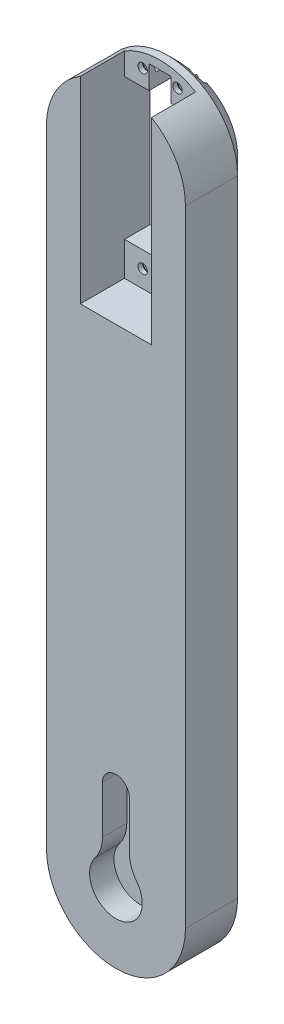
SolidWorks part; units mm, degrees
ref_plane "Front Plane" through (0, 0, 0) normal (0, 0, 1) x (1, 0, 0)
ref_plane "Top Plane" through (0, 0, 0) normal (0, 1, 0) x (1, 0, 0)
ref_plane "Right Plane" through (0, 0, 0) normal (1, 0, 0) x (0, 0, -1)
sketch "Sketch1" plane through (0, 0, 0) normal (0, 0, 1) x (1, 0, 0)
  line L0 (0, 0) -> (0, 147.804) construction
  line L4 (0, 180) -> (0, 0) construction
  line L6 (20, 180) -> (20, 0)
  line L7 (-20, 180) -> (-20, 0)
  arc A1 (20, 180) -> (-20, 180) centre (0, 180) ccw
  arc A2 (-20, 0) -> (20, 0) centre (0, 0) ccw
  point P2 (0, 0)
  point P7 (0, 90)
  dimension "D1" = 180
  dimension "D3" = 40
extrude "Boss-Extrude1" add sketch "Sketch1" along normal mid plane 20
chamfer "Chamfer1" distance 5 angle 45 4 edges at (-20, 90, -10) (0, -20, -10) (20, 90, -10) (0, 200, -10)
sketch "Sketch3" plane through (0, 0, 0) normal (1, 0, 0) x (0, 0, -1)
  line L0 (-10, 170.5) -> (30.3, 170.5) construction
  line L2 (2.7, 190.79) -> (2.7, 200.5)
  line L3 (2.7, 200.5) -> (-10, 200.5)
  line L5 (2.7, 190.79) -> (10, 190.79)
  line L7 (10, 190.79) -> (10, 170.5)
  line L8 (-10, 0) -> (-10, 180) construction
  line L9 (10, 170.5) -> (-10, 170.5)
  line L10 (10, 0) -> (10, 180) construction
  line L11 (-10, 170.5) -> (-10, 200.5)
  line L12 (30.3, 151.5) -> (30.3, 189.5) construction
  line L13 (30.3, 151.5) -> (30.3, 189.5) construction
  dimension "D1" = 20.29
  dimension "D2" = 30
  dimension "D3" = 12.7
extrude "Cut-Extrude1" cut sketch "Sketch3" against normal mid plane 20.5
sketch "Sketch11" plane through (0, 0, -2.7) normal (0, 0, 1) x (1, 0, 0)
  line L0 (-8.25, 195.5) -> (8.25, 195.5) construction
  arc A0 (-7.6279, 197.0532) -> (-4.4736, 197.1531) centre (-6, 195.5) ccw construction
  arc A1 (4.4736, 197.1531) -> (7.6279, 197.0532) centre (6, 195.5) ccw construction
  circle A2 centre (-5, 195.5) radius 2
  dimension "D1" = 4
  dimension "D2" = 1
ref_axis "Axis1" through (-6, 195.5, 15.691) along (0, 0, 1)
ref_plane "Plane1" through (-5, 0, 0) normal (1, 0, 0) x (0, 0, -1)
sketch "Sketch4" plane through (-5, 0, 0) normal (1, 0, 0) x (0, 0, -1)
  line L0 (-15.691, 195.5) -> (-20.7621, 195.5) construction
  line L1 (2.7, 195.5) -> (10, 195.5)
  line L2 (2.7, 190.79) -> (2.7, 197.1737) construction
  line L3 (2.7, 195.5) -> (2.7, 196.85)
  line L4 (2.7, 196.85) -> (4, 196.85)
  line L5 (4, 196.85) -> (4.75, 197.6)
  line L6 (4.75, 197.6) -> (10, 197.6)
  line L7 (10, 197.6) -> (10, 195.5)
  line L8 (10, 180) -> (10, 195) construction
  dimension "D1" = 6
  dimension "D2" = 1.35
  dimension "D3" = 2.1
  dimension "D4" = 135
revolve "Cut-Revolve1" cut sketch "Sketch4" angle 360 about L1 reverse direction yes
ref_plane "Plane2" through (0, 0, 0) normal (1, 0, 0) x (0, 0, -1)
mirror "Mirror1" about plane through (0, 0, 0) normal (1, 0, 0) of "Cut-Revolve1"
mirror "Mirror2" about plane through (-10.25, 170.5, -10) normal (0, -1, 0) of "Cut-Extrude1", "Mirror1"
sketch "Sketch5" plane through (0, 0, -2.7) normal (0, 0, 1) x (1, 0, 0)
  line L0 (-10.25, 190.79) -> (10.25, 190.79) construction
  line L1 (-3.2, 190.79) -> (3.2, 190.79)
  line L2 (-3.2, 190.79) -> (-3.2, 197.5)
  line L3 (-3.2, 197.5) -> (3.2, 197.5)
  line L4 (3.2, 190.79) -> (3.2, 197.5)
  line L7 (3.2, 147.5) -> (3.2, 142.5) construction
  line L8 (-3.2, 147.5) -> (-3.2, 142.5) construction
  dimension "D1" = 6.71
extrude "Cut-Extrude2" cut sketch "Sketch5" against normal blind 24
sketch "Sketch6" plane through (0, 0, 10) normal (0, 0, 1) x (1, 0, 0)
  line L0 (0, 0) -> (0, 24.5) construction
  line L1 (3.875, 24.5) -> (3.875, 10.7873)
  line L2 (-3.875, 24.5) -> (-3.875, 10.7873)
  arc A0 (-5.9803, 4.6494) -> (5.9803, 4.6494) centre (0, 0) ccw
  arc A1 (3.875, 24.5) -> (-3.875, 24.5) centre (0, 24.5) ccw
  arc A2 (-3.875, 10.7873) -> (-5.9803, 4.6494) centre (-13.875, 10.7873) cw
  arc A3 (3.875, 10.7873) -> (5.9803, 4.6494) centre (13.875, 10.7873) ccw
  dimension "D1" = 15.15
  dimension "D3" = 7.75
  dimension "D4" = 10
  dimension "D2" = 24.5
extrude "Cut-Extrude3" cut sketch "Sketch6" against normal blind 7 contours A3 L1 A1 L2 A2 A0 region at (0, 8.1019, 10)
sketch "Sketch10" plane through (0, 0, -10) normal (0, 0, -1) x (-1, 0, 0)
  line L0 (0, 0) -> (0, 93.1642) construction
  line L1 (10.25, 140.5) -> (-10.25, 140.5) construction
  line L2 (-5, -21) -> (5, -21)
  line L3 (-5, -21) -> (-5, 137.5)
  line L4 (-5, 137.5) -> (5, 137.5)
  line L5 (5, -21) -> (5, 137.5)
  line L6 (-5, -21) -> (5, 137.5) construction
  line L7 (-5, 137.5) -> (5, -21) construction
  arc A0 (-20, 0) -> (20, 0) centre (0, 0) ccw construction
  point P3 (0, 58.25)
  dimension "D1" = 3
  dimension "D2" = 10
  dimension "D3" = 1
extrude "Cut-Extrude6" cut sketch "Sketch10" against normal blind 11
chamfer "Chamfer2" distance 5 angle 45 2 edges at (5, 59.0675, 1) (-5, 59.0675, 1)
sketch "Sketch7" plane through (0, 0, -10) normal (0, 0, -1) x (-1, 0, 0)
  circle A0 centre (0, 0) radius 4
  circle A1 centre (0, 24.5) radius 4
  dimension "D1" = 8
extrude "Cut-Extrude4" cut sketch "Sketch7" against normal blind 11
sketch "Sketch8" plane through (0, 0, 1) normal (0, 0, -1) x (-1, 0, 0)
  circle A0 centre (0, 24.5) radius 1.5
  circle A1 centre (0, 0) radius 1.5
  dimension "D1" = 3
extrude "Cut-Extrude5" cut sketch "Sketch8" against normal blind 11
